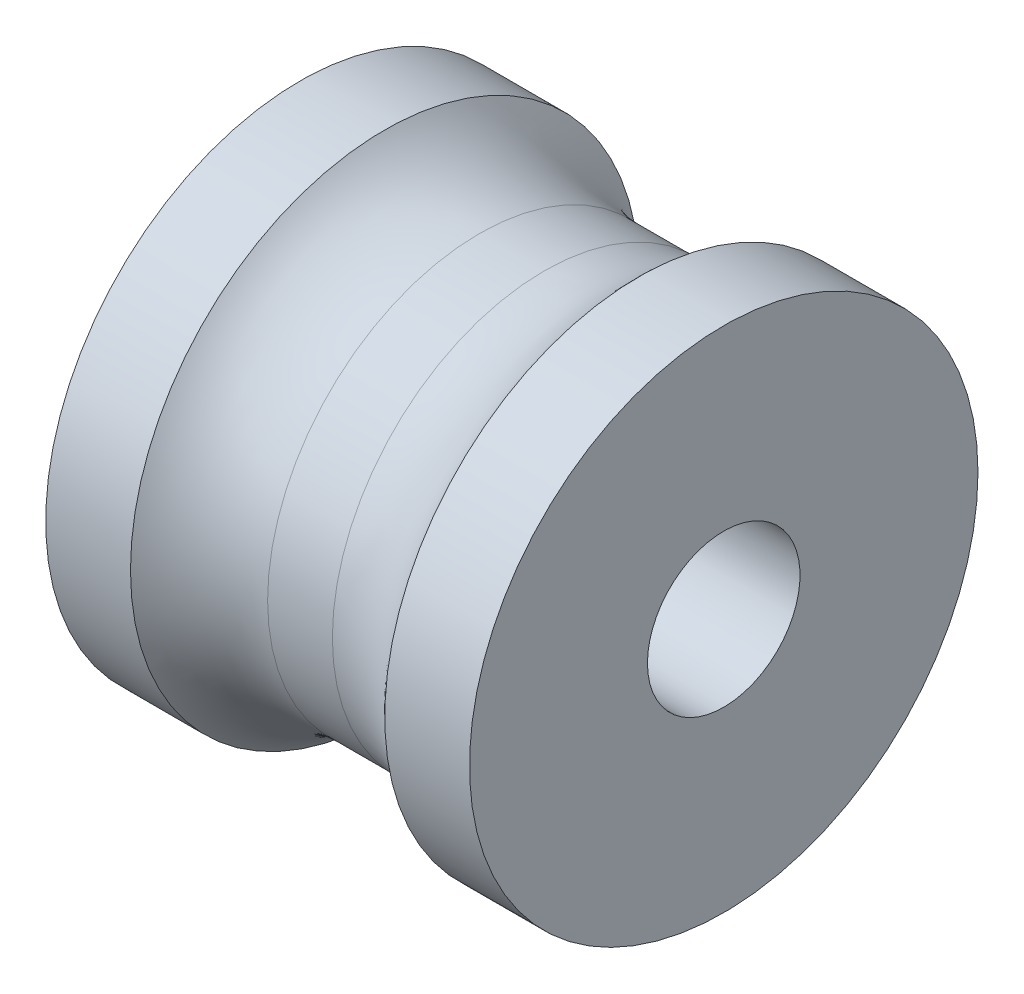
SolidWorks part; units mm, degrees
ref_plane "Front Plane" through (0, 0, 0) normal (0, 0, 1) x (1, 0, 0)
ref_plane "Top Plane" through (0, 0, 0) normal (0, 1, 0) x (1, 0, 0)
ref_plane "Right Plane" through (0, 0, 0) normal (1, 0, 0) x (0, 0, -1)
sketch "Sketch1" plane through (0, 0, 0) normal (1, 0, 0) x (0, 0, -1)
  circle A0 centre (0, 0) radius 6
  dimension "D1" = 12
extrude "Boss-Extrude1" add sketch "Sketch1" along normal blind 2
sketch "Sketch2" plane through (2, 0, 0) normal (1, 0, 0) x (0, 0, -1)
  circle A0 centre (0, 0) radius 5
  dimension "D1" = 10
extrude "Boss-Extrude2" add sketch "Sketch2" along normal blind 6
sketch "Sketch3" plane through (8, 0, 0) normal (1, 0, 0) x (0, 0, -1)
  circle A0 centre (0, 0) radius 6
  dimension "D1" = 12
extrude "Boss-Extrude3" add sketch "Sketch3" along normal blind 2
fillet "Fillet1" radius 3 2 edges at (8, 0, -5) (2, 0, -5)
sketch "Sketch4" plane through (0, 0, 0) normal (-1, 0, 0) x (0, 0, 1)
  circle A0 centre (0, 0) radius 1.8
  dimension "D1" = 3.6
extrude "Cut-Extrude1" cut sketch "Sketch4" against normal through all
equation "\"滑动-垂直孔\"= 0.6"
equation "\"滑动-水平孔\"= 0.3"
equation "\"松动-垂直孔\"= 0.3"
equation "\"松动-水平孔\"= 0.1"
equation "\"正常-垂直孔\"= 0.15"
equation "\"正常-水平孔\"= 0"
equation "\"紧缩-垂直孔\"= 0"
equation "\"紧缩-水平孔\"= - 0.1"
equation "\"D1@Sketch4\"=\"滑动-垂直孔\"+3"
